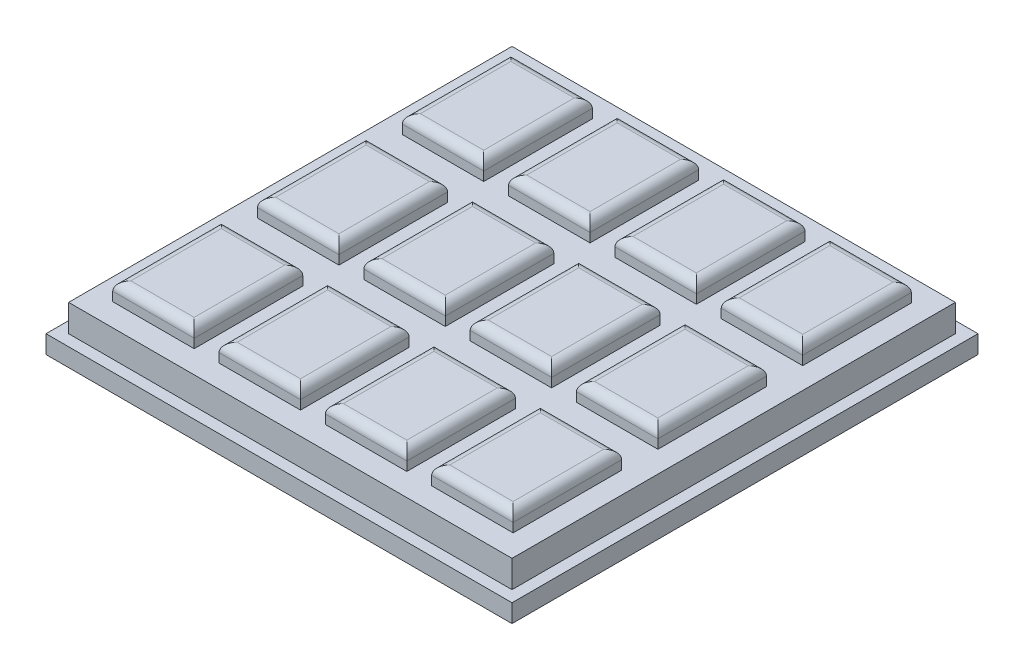
SolidWorks part; units mm, degrees
material "NEOPRENE"
ref_plane "Front Plane" through (0, 0, 0) normal (0, 0, 1) x (1, 0, 0)
ref_plane "Top Plane" through (0, 0, 0) normal (0, 1, 0) x (1, 0, 0)
ref_plane "Right Plane" through (0, 0, 0) normal (1, 0, 0) x (0, 0, -1)
sketch "Sketch1" plane through (0, 0, 0) normal (0, 1, 0) x (1, 0, 0)
  line L1 (-24.5, 24.5) -> (24.5, 24.5)
  line L2 (-24.5, 24.5) -> (-24.5, -24.5)
  line L3 (-24.5, -24.5) -> (24.5, -24.5)
  line L4 (24.5, 24.5) -> (24.5, -24.5)
  line L5 (-24.5, 24.5) -> (24.5, -24.5) construction
  line L6 (-24.5, -24.5) -> (24.5, 24.5) construction
  point P0 (0, 0)
  dimension "D1" = 49
  dimension "D2" = 49
extrude "Boss-Extrude1" add sketch "Sketch1" along normal blind 3
sketch "Sketch2" plane through (0, 3, 0) normal (0, 1, 0) x (1, 0, 0)
  line L0 (-11.75, 23.5) -> (-23.5, 8.5)
  line L1 (-23.5, 23.5) -> (23.5, 23.5)
  line L2 (-23.5, 23.5) -> (-23.5, -23.5)
  line L3 (-23.5, -23.5) -> (23.5, -23.5)
  line L4 (23.5, 23.5) -> (23.5, -23.5)
  line L5 (-23.5, 23.5) -> (23.5, -23.5) construction
  line L6 (-23.5, -23.5) -> (23.5, 23.5) construction
  line L7 (-23.5, 23.5) -> (-11.75, 23.5)
  line L8 (-23.5, 23.5) -> (-23.5, 8.5)
  line L9 (-23.5, 8.5) -> (-11.75, 8.5)
  line L10 (-11.75, 23.5) -> (-11.75, 8.5)
  line L12 (-22.125, 22) -> (-13.125, 22)
  line L13 (-22.125, 22) -> (-22.125, 10)
  line L14 (-22.125, 10) -> (-13.125, 10)
  line L15 (-13.125, 22) -> (-13.125, 10)
  line L16 (-22.125, 22) -> (-13.125, 10) construction
  line L17 (-22.125, 10) -> (-13.125, 22) construction
  point P1 (0, 0)
  point P9 (-17.625, 16)
  dimension "D1" = 47
  dimension "D2" = 47
  dimension "D3" = 15
  dimension "D4" = 11.75
  dimension "D5" = 9
  dimension "D6" = 12
extrude "Boss-Extrude2" add sketch "Sketch2" along normal blind 2 contours L13 L12 L15 L14
fillet "Fillet1" radius 1 4 edges at (-13.125, 5, -16) (-17.625, 5, -22) (-22.125, 5, -16) (-17.625, 5, -10)
pattern_linear "LPattern1" count 4 spacing 11.75 along (1, 0, 0) count 3 spacing 16 along (0, 0, 1) of "Fillet1", "Boss-Extrude2"
sketch "Sketch3" plane through (0, 0, 0) normal (0, -1, 0) x (1, 0, 0)
  line L0 (-24.5, -24.5) -> (-24.5, 24.5) construction
  line L1 (-25.75, 25.75) -> (25.75, 25.75)
  line L2 (-25.75, 25.75) -> (-25.75, -25.75)
  line L3 (-25.75, -25.75) -> (25.75, -25.75)
  line L4 (25.75, 25.75) -> (25.75, -25.75)
  line L5 (-25.75, 25.75) -> (25.75, -25.75) construction
  line L6 (-25.75, -25.75) -> (25.75, 25.75) construction
  line L7 (-24.5, 24.5) -> (24.5, 24.5) construction
  point P0 (0, 0)
  dimension "D1" = 1.25
  dimension "D2" = 1.25
extrude "Boss-Extrude3" add sketch "Sketch3" along normal blind 2
